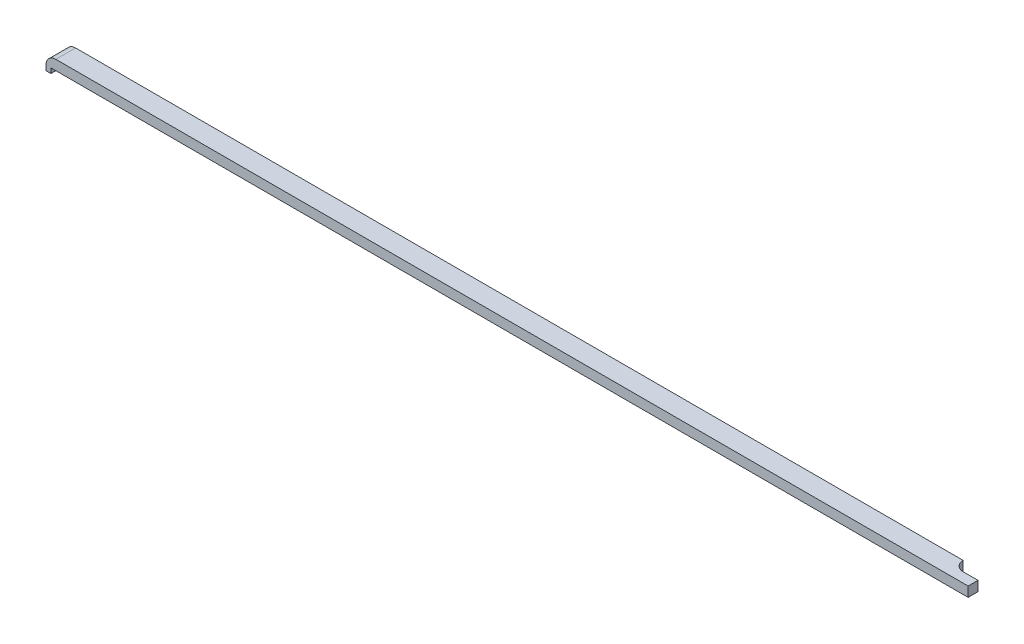
SolidWorks part; units mm, degrees
ref_plane "前视基准面" through (0, 0, 0) normal (0, 0, 1) x (1, 0, 0)
ref_plane "上视基准面" through (0, 0, 0) normal (0, 1, 0) x (1, 0, 0)
ref_plane "右视基准面" through (0, 0, 0) normal (1, 0, 0) x (0, 0, -1)
sketch "草图1" plane through (0, 0, 0) normal (0, 0, 1) x (1, 0, 0)
  line L0 (0, 0) -> (187, 0)
  line L1 (55, 0) -> (-55, 0) construction
  dimension "D1" = 187
extrude "拉伸-薄壁1" add sketch "草图1" along normal blind 4 thin thin type one direction wall 2
sketch "草图2" plane through (0, -2, 0) normal (0, -1, 0) x (1, 0, 0)
  line L0 (0, -1.1) -> (0, 1.1) construction
  line L1 (0, 4) -> (1, 4)
  line L2 (0, 4) -> (0, 0)
  line L3 (0, 0) -> (1, 0)
  line L4 (1, 4) -> (1, 0)
  line L5 (0, 4) -> (187, 4) construction
  line L6 (1.1, 0) -> (-1.1, 0) construction
  dimension "D1" = 1
extrude "凸台-拉伸1" add sketch "草图2" along normal blind 1
fillet "圆角1" radius 2 1 edges at (0, 0, 2)
sketch "草图3" plane through (0, -2, 0) normal (0, -1, 0) x (1, 0, 0)
  line L0 (187, 4) -> (187, 0) construction
  line L1 (187, 0) -> (182, 0)
  line L2 (187, 0) -> (187, 2)
  line L3 (187, 2) -> (182, 2)
  line L4 (182, 0) -> (182, 2)
  line L5 (1.65, 0) -> (-1.65, 0) construction
  line L6 (1, 4) -> (187, 4) construction
  point P6 (187, 0.4229)
  dimension "D1" = 5
  dimension "D2" = 2
extrude "切除-拉伸1" cut sketch "草图3" against normal through all
fillet "圆角2" radius 2 1 edges at (182, -1, 2)
